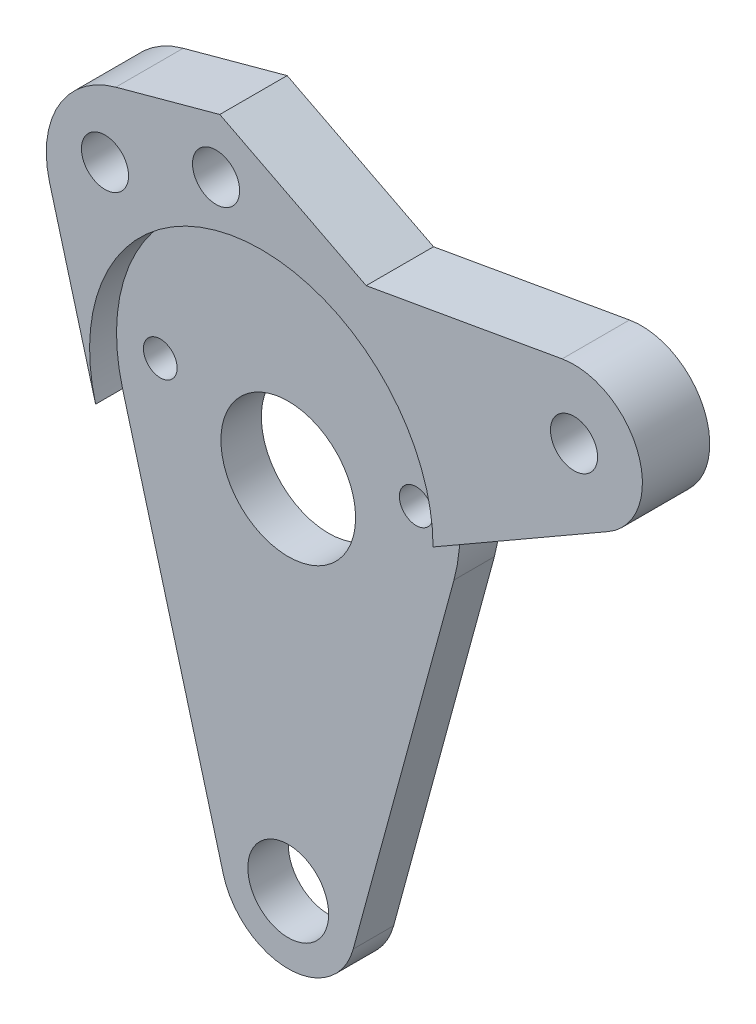
SolidWorks part; units mm, degrees
ref_plane "Front Plane" through (0, 0, 0) normal (0, 0, 1) x (1, 0, 0)
ref_plane "Top Plane" through (0, 0, 0) normal (0, 1, 0) x (1, 0, 0)
ref_plane "Right Plane" through (0, 0, 0) normal (1, 0, 0) x (0, 0, -1)
sketch "Sketch1" plane through (0, 0, 0) normal (0, 0, 1) x (1, 0, 0)
  line L0 (0, 0) -> (0, -29.5) construction
  line L1 (-4.8244, -30.8136) -> (-12.3021, -3.3496)
  line L2 (4.8244, -30.8136) -> (12.3021, -3.3496)
  line L3 (-9.5, 0) -> (9.5, 0) construction
  arc A0 (12.3021, -3.3496) -> (-12.3021, -3.3496) centre (0, 0) ccw
  arc A1 (-4.8244, -30.8136) -> (4.8244, -30.8136) centre (0, -29.5) ccw
  circle A2 centre (0, -29.5) radius 3
  circle A3 centre (0, -3) radius 5
  circle A4 centre (-9.5, 0) radius 1.25
  circle A5 centre (9.5, 0) radius 1.25
  dimension "D1" = 25.5
  dimension "D2" = 10
  dimension "D4" = 6
  dimension "D7" = 10
  dimension "D8" = 2.5
  dimension "D3" = 29.5
  dimension "D5" = 19
  dimension "D6" = 3
  dimension "D9" = 26.5
extrude "Boss-Extrude1" add sketch "Sketch1" along normal blind 3
sketch "Sketch2" plane through (0, 0, 0) normal (0, 0, 1) x (1, 0, 0)
  line L0 (-2.214, 12.5563) -> (22.3334, 16.8847)
  line L1 (0, 0) -> (12.75, 0) construction
  line L2 (25.7485, 7.4859) -> (12.75, 0)
  arc A0 (12.3021, -3.3496) -> (-12.3021, -3.3496) centre (0, 0) ccw construction
  arc A1 (12.75, 0) -> (-2.214, 12.5563) centre (0, 0) ccw
  arc A2 (22.3334, 16.8847) -> (25.7485, 7.4859) centre (23.215, 11.8852) cw
  circle A4 centre (23.215, 11.8852) radius 1.75
  dimension "D4" = 3.5
  dimension "D1" = 10
  dimension "D2" = 10
  dimension "D3" = 15
extrude "Boss-Extrude2" add sketch "Sketch2" along normal blind 5
sketch "Sketch4" plane through (0, 0, 0) normal (0, 0, 1) x (1, 0, 0)
  line L0 (-12.3021, -3.3496) -> (-15.7174, 9.1938)
  line L1 (-10.8023, 17.7869) -> (-3.0833, 19.8886)
  line L2 (-3.0833, 19.8886) -> (7.786, 14.3196)
  line L3 (22.3334, 16.8847) -> (-2.214, 12.5563) construction
  line L5 (7.786, 14.3196) -> (-2.214, 12.5563)
  line L6 (-12.3021, -3.3496) -> (-4.8244, -30.8136) construction
  arc A0 (-2.214, 12.5563) -> (-12.3021, -3.3496) centre (0, 0) ccw construction
  arc A2 (-2.214, 12.5563) -> (-12.3021, -3.3496) centre (0, 0) ccw
  arc A3 (-15.7174, 9.1938) -> (-10.8023, 17.7869) centre (-8.9633, 11.0328) cw
  circle A4 centre (-11.6058, 12.5563) radius 1.75
  circle A5 centre (-3.3596, 15.7172) radius 1.75
  point P19 (-17.5564, 15.9479)
  point P22 (-11.6058, 12.5563)
  point P23 (-3.3596, 15.7172)
  dimension "D1" = 15
  dimension "D3" = 10
  dimension "D4" = 7
  dimension "D5" = 3.5
  dimension "D2" = 20
extrude "Boss-Extrude3" add sketch "Sketch4" along normal blind 5
